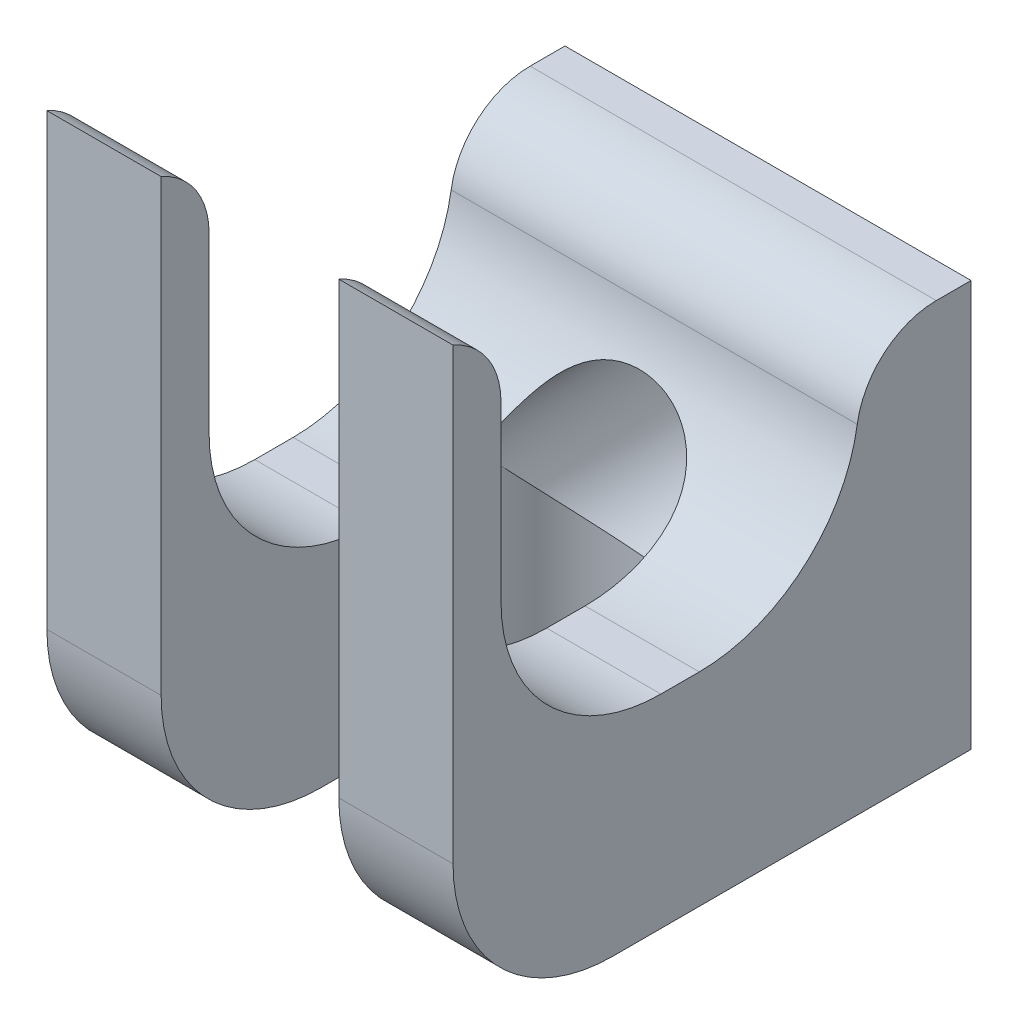
SolidWorks part; units mm, degrees
ref_plane "Front Plane" through (0, 0, 0) normal (0, 0, 1) x (1, 0, 0)
ref_plane "Top Plane" through (0, 0, 0) normal (0, 1, 0) x (1, 0, 0)
ref_plane "Right Plane" through (0, 0, 0) normal (1, 0, 0) x (0, 0, -1)
sketch "Sketch1" plane through (0, 0, 0) normal (0, 0, 1) x (1, 0, 0)
  line L1 (12.7, -12.7) -> (-12.7, -12.7)
  line L2 (12.7, -12.7) -> (12.7, 12.7)
  line L3 (12.7, 12.7) -> (-12.7, 12.7)
  line L4 (-12.7, -12.7) -> (-12.7, 12.7)
  line L5 (12.7, -12.7) -> (-12.7, 12.7) construction
  line L6 (12.7, 12.7) -> (-12.7, -12.7) construction
  point P0 (0, 0)
  dimension "D1" = 25.4
  dimension "D2" = 25.4
extrude "Boss-Extrude1" add sketch "Sketch1" along normal blind 7
hole_wizard "CBORE for 1/4 Socket Head Cap Screw1" positions "Sketch2" profile "Sketch3" counterbore size "1/4" standard "ANSI Inch" end condition through all
sketch "Sketch2" plane through (0, 0, 7) normal (0, 0, 1) x (1, 0, 0)
  point P0 (0, 0)
sketch "Sketch3" plane through (0, 0, 7) normal (1, 0, 0) x (0, -1, 0)
  line L0 (0, 0) -> (0, 7)
  line L1 (0, 7) -> (3.3782, 7)
  line L3 (3.3782, 7) -> (3.3782, 6.35)
  line L4 (3.3782, 6.35) -> (5.5562, 6.35)
  line L5 (5.5562, 6.35) -> (5.5562, 0)
  line L7 (5.5562, 0) -> (0, 0)
  line L11 (0, -6.35) -> (0, 107.95) construction
  dimension "Thru Hole Dia." = 6.7564
  dimension "Thru Hole Depth" = 7
  dimension "C'Bore Dia." = 11.1125
  dimension "C'Bore Depth" = 6.35
sketch "Sketch4" plane through (0, 0, 7) normal (0, 0, 1) x (1, 0, 0)
  line L1 (-12.7, -12.7) -> (-5.5562, -12.7)
  line L2 (-12.7, -12.7) -> (-12.7, 0)
  line L3 (-12.7, 0) -> (-5.5562, 0)
  line L4 (-5.5562, -12.7) -> (-5.5562, 0)
  line L5 (12.7, -12.7) -> (5.5562, -12.7)
  line L6 (12.7, -12.7) -> (12.7, 0)
  line L7 (12.7, 0) -> (5.5562, 0)
  line L8 (5.5562, -12.7) -> (5.5562, 0)
  circle A0 centre (0, 0) radius 5.5562 construction
  circle A1 centre (0, 0) radius 5.5562 construction
extrude "Boss-Extrude2" add sketch "Sketch4" along normal blind 25.4
sketch "Sketch5" plane through (0, 0, 0) normal (0, 1, 0) x (1, 0, 0)
  line L0 (-12.7, -32.4) -> (-12.7, -7) construction
  line L1 (-5.5562, -32.4) -> (-12.7, -32.4)
  line L2 (-5.5562, -32.4) -> (-5.5562, -29.4)
  line L3 (-5.5562, -29.4) -> (-12.7, -29.4)
  line L4 (-12.7, -32.4) -> (-12.7, -29.4)
  line L5 (12.7, -32.4) -> (12.7, -7) construction
  line L6 (5.5562, -32.4) -> (12.7, -32.4)
  line L7 (5.5562, -32.4) -> (5.5562, -29.4)
  line L8 (5.5562, -29.4) -> (12.7, -29.4)
  line L9 (12.7, -32.4) -> (12.7, -29.4)
  dimension "D1" = 3
  dimension "D2" = 3
extrude "Boss-Extrude3" add sketch "Sketch5" along normal blind 25.4
fillet "Fillet1" radius 10 5 edges at (9.1281, 0, 7) (-9.1281, 0, 29.4) (9.1281, 0, 29.4) (-9.1281, -12.7, 32.4) (9.1281, -12.7, 32.4)
fillet "Fillet2" radius 5 5 edges at (5.5562, -6.35, 7) (-5.5562, -6.35, 7) (-9.1281, 25.4, 29.4) (9.1281, 25.4, 29.4) (0, 12.7, 7)
